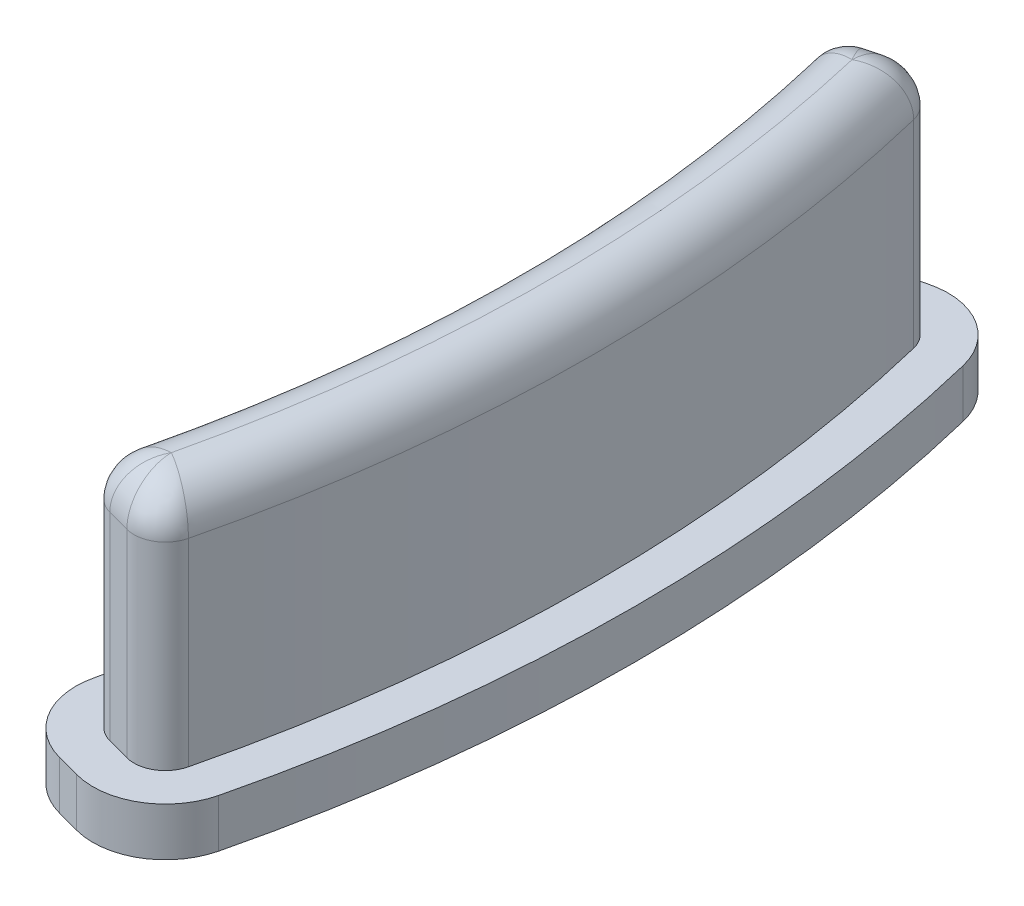
SolidWorks part; units mm, degrees
material "ABS"
ref_plane "Front Plane" through (0, 0, 0) normal (0, 0, 1) x (1, 0, 0)
ref_plane "Top Plane" through (0, 0, 0) normal (0, 1, 0) x (1, 0, 0)
ref_plane "Right Plane" through (0, 0, 0) normal (1, 0, 0) x (0, 0, -1)
sketch "Эскиз1" plane through (0, 0, 0) normal (0, 1, 0) x (1, 0, 0)
  line L2 (-0.8495, -7.8597) -> (-0.3664, -7.9892)
  line L3 (-0.8495, 7.8597) -> (-0.3664, 7.9892)
  arc A6 (-0.3664, -7.9892) -> (0.4336, -7.5144) centre (-0.1981, -7.3613) ccw
  arc A7 (0.4336, 7.5144) -> (0.4336, -7.5144) centre (-30.5687, 0) cw
  arc A8 (0.4336, 7.5144) -> (-0.3664, 7.9892) centre (-0.1981, 7.3613) ccw
  arc A9 (-0.8495, 7.8597) -> (-1.313, 7.079) centre (-0.6813, 7.2319) ccw
  arc A10 (-1.313, 7.079) -> (-1.313, -7.079) centre (-30.5687, 0) cw
  arc A11 (-0.8495, -7.8597) -> (-1.313, -7.079) centre (-0.6813, -7.2319) cw
  point P13 (0.3409, 8.2822)
  point P14 (0.3409, -8.2822)
  dimension "D4" = 0.3409
extrude "Бобышка-Вытянуть1" add sketch "Эскиз1" along normal blind 6
sketch "Эскиз2" plane through (0, 0, 0) normal (0, -1, 0) x (1, 0, 0)
  line L4 (-1.0695, 8.6808) -> (-0.5864, 8.8102)
  line L5 (-0.5864, -8.8102) -> (-1.0695, -8.6808)
  arc A12 (1.2596, 7.7147) -> (-0.5864, 8.8102) centre (-0.1981, 7.3613) ccw
  arc A13 (1.2596, -7.7147) -> (1.2596, 7.7147) centre (-30.5687, 0) ccw
  arc A14 (-0.5864, -8.8102) -> (1.2596, -7.7147) centre (-0.1981, -7.3613) ccw
  arc A15 (-2.1392, -6.8791) -> (-1.0695, -8.6808) centre (-0.6813, -7.2319) ccw
  arc A16 (-2.1392, -6.8791) -> (-2.1392, 6.8791) centre (-30.5687, 0) ccw
  arc A17 (-1.0695, 8.6808) -> (-2.1392, 6.8791) centre (-0.6813, 7.2319) ccw
  point P27 (0, 0)
extrude "Бобышка-Вытянуть2" add sketch "Эскиз2" against normal blind 1
fillet "Скругление1" radius 0.9 8 edges at (0.1336, 6, 7.9203) (-0.6079, 6, 7.9244) (-1.2402, 6, 7.5637) (-0.4687, 6, 0) (-1.2402, 6, -7.5637) (-0.6079, 6, -7.9244) (0.1336, 6, -7.9203) (1.3313, 6, 0)
